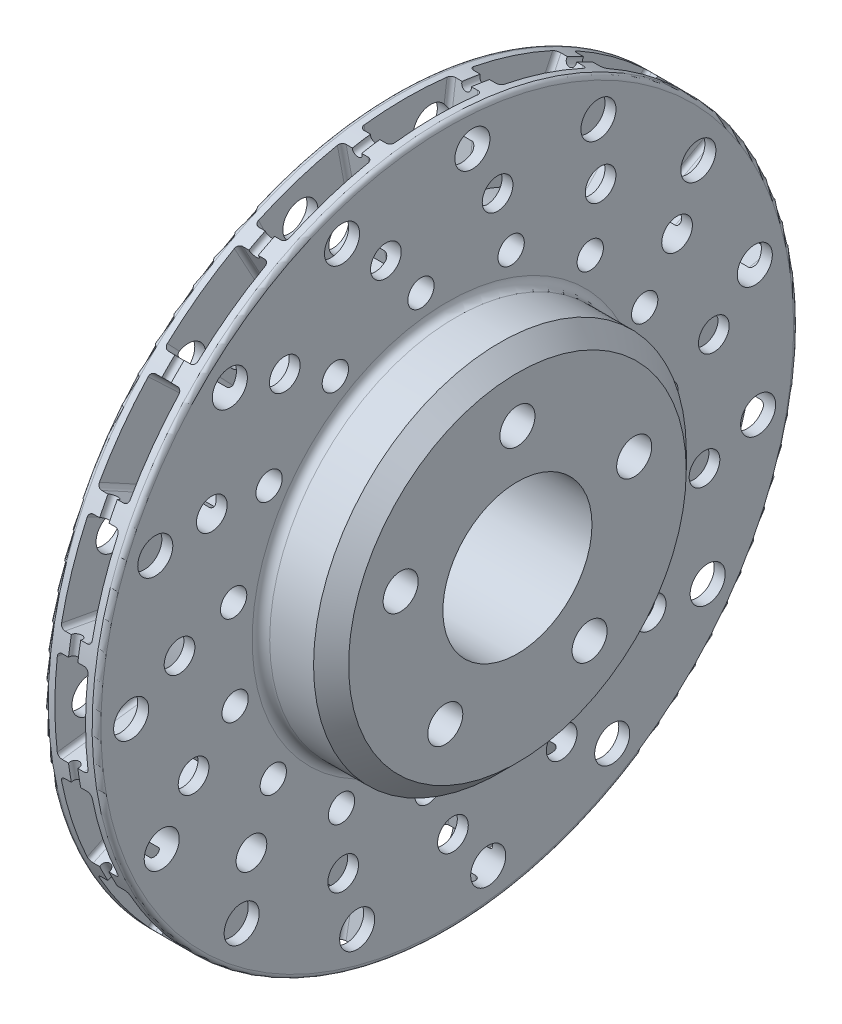
SolidWorks part; units mm, degrees
material "Gray Cast Iron"
ref_plane "Front Plane" through (0, 0, 0) normal (0, 0, 1) x (1, 0, 0)
ref_plane "Top Plane" through (0, 0, 0) normal (0, 1, 0) x (1, 0, 0)
ref_plane "Right Plane" through (0, 0, 0) normal (1, 0, 0) x (0, 0, -1)
sketch "Sketch1" plane through (0, 0, 0) normal (1, 0, 0) x (0, 0, -1)
  circle A0 centre (0, 0) radius 200
  dimension "D1" = 400
extrude "Boss-Extrude1" add sketch "Sketch1" along normal mid plane 30
sketch "Sketch2" plane through (15, 0, 0) normal (1, 0, 0) x (0, 0, -1)
  circle A0 centre (0, 0) radius 106.25
  dimension "D1" = 212.5
extrude "Boss-Extrude2" add sketch "Sketch2" along normal blind 40
sketch "Sketch3" plane through (55, 0, 0) normal (1, 0, 0) x (0, 0, -1)
  line L0 (0, 0) -> (0, 70) construction
  circle A0 centre (0, 70) radius 10
  circle A1 centre (66.574, 21.6312) radius 10
  circle A2 centre (41.145, -56.6312) radius 10
  circle A3 centre (-41.145, -56.6312) radius 10
  circle A4 centre (-66.574, 21.6312) radius 10
  circle A5 centre (0, 0) radius 42.5
  point P14 (0, 0)
  dimension "D2" = 20
  dimension "D4" = 85
  dimension "D1" = 70
  dimension "D3" = 5
extrude "Cut-Extrude1" cut sketch "Sketch3" against normal through all
sketch "Sketch4" plane through (0, 0, 0) normal (0, 0, 1) x (1, 0, 0)
  line L0 (0, 200) -> (0, 164.9312) construction
  line L1 (15, 200) -> (-15, 200) construction
  line L2 (-8.75, 200) -> (8.75, 200)
  line L3 (8.75, 200) -> (8.75, 140)
  line L4 (8.75, 140) -> (-8.75, 140)
  line L5 (-8.75, 140) -> (-8.75, 200)
  line L6 (0, 0) -> (-65.6601, 0) construction
  point P8 (0, 200)
  dimension "D1" = 17.5
  dimension "D2" = 60
revolve "Cut-Revolve1" cut sketch "Sketch4" angle 15 mid plane about L6
fillet "Fillet1" radius 2.5 4 edges at (8.75, 168.5456, 22.1895) (-8.75, 168.5456, 22.1895) (8.75, 168.5456, -22.1895) (-8.75, 168.5456, -22.1895)
pattern_circular "CirPattern1" count 20 over 360 about axis through (-15, 0, 0) along (1, 0, 0) of "Cut-Revolve1", "Fillet1"
sketch "Sketch5" plane through (15, 0, 0) normal (1, 0, 0) x (0, 0, -1)
  arc A0 (0, 0) -> (-60, 170) centre (-143.0606, 45.0963) ccw construction
  circle A1 centre (-60, 170) radius 10
  circle A2 centre (-35, 149.1295) radius 8.75
  circle A3 centre (-15, 123.2019) radius 7.5
  point P9 (0, 0)
  dimension "D1" = 150
  dimension "D4" = 20
  dimension "D5" = 17.5
  dimension "D7" = 15
  dimension "D2" = 170
  dimension "D3" = 60
  dimension "D6" = 25
  dimension "D8" = 20
extrude "Cut-Extrude2" cut sketch "Sketch5" against normal through all
pattern_circular "CirPattern2" count 15 over 360 about axis through (55, 0, 0) along (1, 0, 0) of "Cut-Extrude2"
fillet "Fillet2" radius 5 1 edges at (15, 0, -106.25)
chamfer "Chamfer1" distance 10 angle 45 1 edges at (55, 0, -106.25)
sketch "Sketch6" plane through (0, 0, 0) normal (0, 0, 1) x (1, 0, 0)
  line L1 (0, 0) -> (45, 0) construction
  line L2 (45, -106.25) -> (45, 106.25) construction
  line L4 (6.25, 198.289) -> (-6.25, 198.289) construction
  circle A0 centre (0, 199.289) radius 2.75
  dimension "D1" = 5.5
  dimension "D2" = 1
revolve "Cut-Revolve3" cut sketch "Sketch6" angle 360 about L1
fillet "Fillet3" radius 2.5 2 edges at (-15, 0, -200) (15, 0, -200)
